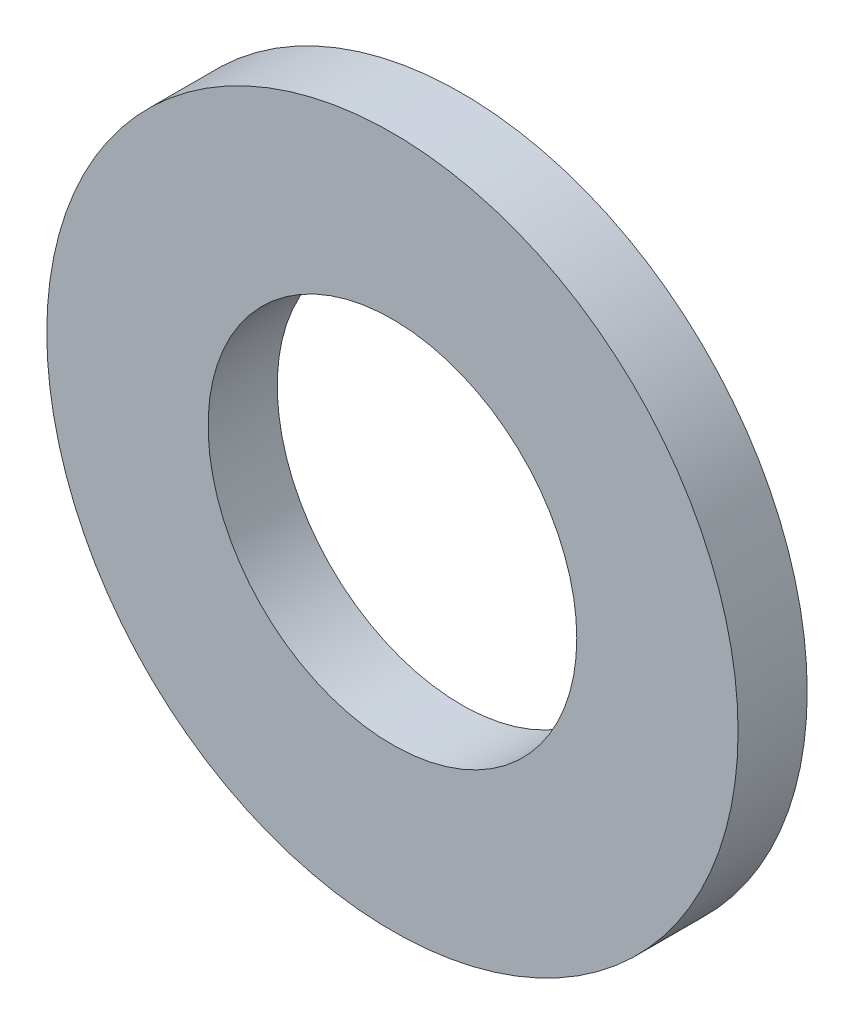
SolidWorks part; units mm, degrees
ref_plane "Front Plane" through (0, 0, 0) normal (0, 0, 1) x (1, 0, 0)
ref_plane "Top Plane" through (0, 0, 0) normal (0, 1, 0) x (1, 0, 0)
ref_plane "Right Plane" through (0, 0, 0) normal (1, 0, 0) x (0, 0, -1)
sketch "Sketch1" plane through (0, 0, 0) normal (0, 0, 1) x (1, 0, 0)
  circle A0 centre (0, 0) radius 7.5
  circle A1 centre (0, 0) radius 4
  circle A2 centre (0, 0) radius 17.526 construction
  circle A3 centre (17.526, 0) radius 1.651
  dimension "OD (d2)" = 15
  dimension "ID (d1)" = 8
  dimension "Circle Dia (d4)" = 35.052
  dimension "Hole Dia (d5)" = 3.302
sketch "Sketch2" plane through (0, 0, 0) normal (0, 0, 1) x (1, 0, 0)
  circle A0 centre (0, 0) radius 4 construction
  circle A1 centre (0, 0) radius 7.5 construction
  circle A2 centre (0, 0) radius 4
  circle A3 centre (0, 0) radius 7.5
extrude "Body Extrude" add sketch "Sketch2" along normal mid plane 1.5
sketch "Sketch3" plane through (0, 0, 0) normal (0, 0, 1) x (1, 0, 0)
  circle A0 centre (17.526, 0) radius 1.651 construction
  circle A1 centre (17.526, 0) radius 1.651
extrude "Hole Cut" [suppressed] cut sketch "Sketch3" against normal through all both and the other way through all
ref_axis "Center Axis 1" through (0, 0, 0.75) along (0, 0, -1)
ref_plane "Contact Plane 1" through (0, 0, -0.75) normal (0, 0, -1) x (-1, 0, 0)
